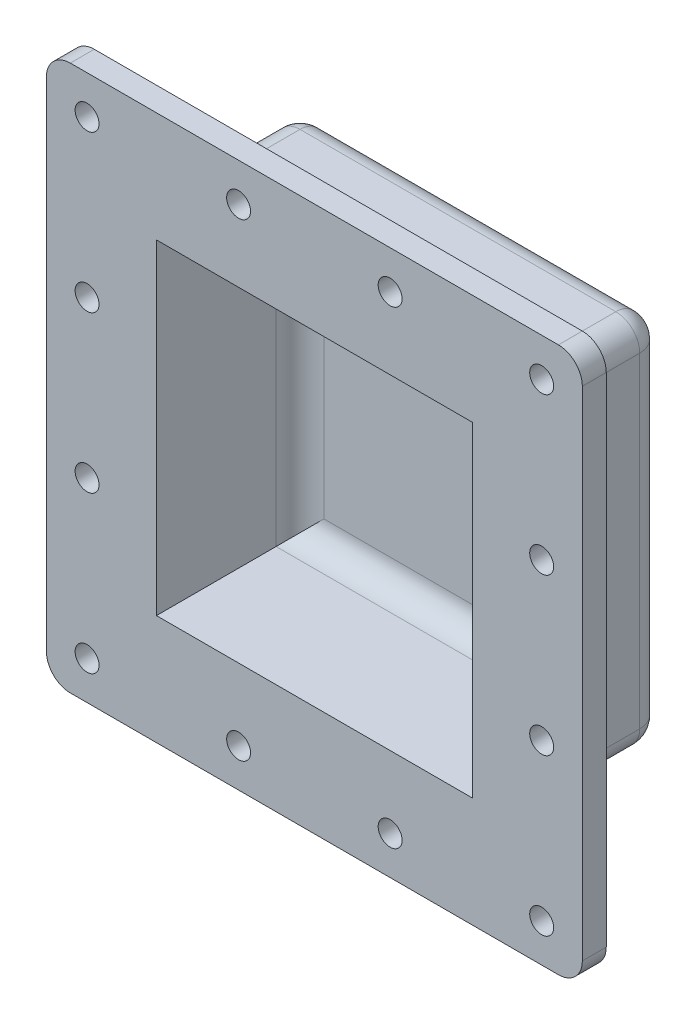
SolidWorks part; units mm, degrees
ref_plane "Front Plane" through (0, 0, 0) normal (0, 0, 1) x (1, 0, 0)
ref_plane "Top Plane" through (0, 0, 0) normal (0, 1, 0) x (1, 0, 0)
ref_plane "Right Plane" through (0, 0, 0) normal (1, 0, 0) x (0, 0, -1)
sketch "Sketch1" plane through (0, 0, 0) normal (0, 0, 1) x (1, 0, 0)
  line L1 (-19, 19.5) -> (19, 19.5)
  line L2 (-19, 19.5) -> (-19, -19.5)
  line L3 (-19, -19.5) -> (19, -19.5)
  line L4 (19, 19.5) -> (19, -19.5)
  line L5 (-19, 19.5) -> (19, -19.5) construction
  line L6 (-19, -19.5) -> (19, 19.5) construction
  point P0 (0, 0)
  dimension "D1" = 38
  dimension "D2" = 39
extrude "Boss-Extrude1" add sketch "Sketch1" along normal blind 15
sketch "Sketch2" plane through (0, 0, 15) normal (0, 0, 1) x (1, 0, 0)
  line L0 (-19, 19.5) -> (-19, -19.5) construction
  line L1 (-28, 28.5) -> (28, 28.5)
  line L2 (-28, 28.5) -> (-28, -28.5)
  line L3 (-28, -28.5) -> (28, -28.5)
  line L4 (28, 28.5) -> (28, -28.5)
  line L5 (-28, 28.5) -> (28, -28.5) construction
  line L6 (-28, -28.5) -> (28, 28.5) construction
  line L7 (-19, 19.5) -> (19, 19.5) construction
  point P0 (0, 0)
  dimension "D1" = 9
  dimension "D2" = 9
extrude "Boss-Extrude2" add sketch "Sketch2" along normal blind 2.5
shell "Shell1" thickness 2.5 removed face at (0, 0, 17.5)
fillet "Fillet1" radius 2.5 4 edges at (-28, -28.5, 16.25) (28, -28.5, 16.25) (28, 28.5, 16.25) (-28, 28.5, 16.25)
fillet "Fillet2" radius 2.5 12 edges at (0, -17, 2.5) (16.5, 0, 2.5) (-16.5, 0, 2.5) (0, 17, 2.5) (0, -19.5, 0) (19, 0, 0) (0, 19.5, 0) (-19, 0, 0) (19, -19.5, 7.5) (19, 19.5, 7.5) (-19, -19.5, 7.5) (-19, 19.5, 7.5)
sketch "Sketch3" plane through (0, 0, 2.5) normal (0, 0, 1) x (1, 0, 0)
  line L1 (-7.5, 14) -> (7.5, 14)
  line L2 (-7.5, 14) -> (-7.5, 6)
  line L3 (-7.5, 6) -> (7.5, 6)
  line L4 (7.5, 14) -> (7.5, 6)
  line L5 (-7.5, 14) -> (7.5, 6) construction
  line L6 (-7.5, 6) -> (7.5, 14) construction
  point P0 (0, 10)
  dimension "D1" = 8
  dimension "D2" = 15
  dimension "D3" = 10
extrude "Cut-Extrude1" cut sketch "Sketch3" against normal through all
sketch "Sketch4" plane through (0, 0, 17.5) normal (0, 0, 1) x (1, 0, 0)
  line L1 (-19, 19.5) -> (-19, -19.5) construction
  line L2 (-19, 19.5) -> (19, 19.5) construction
  line L3 (-23.75, 24.5) -> (23.75, 24.5) construction
  line L10 (-23.75, 24.5) -> (-23.75, -24.5) construction
  line L11 (-23.75, -24.5) -> (23.75, -24.5) construction
  line L18 (23.75, 24.5) -> (23.75, -24.5) construction
  line L19 (-23.75, 24.5) -> (23.75, -24.5) construction
  line L20 (-23.75, -24.5) -> (23.75, 24.5) construction
  circle A21 centre (-23.75, 24.5) radius 1.25
  circle A25 centre (-7.9167, 24.5) radius 1.25
  circle A26 centre (7.9167, 24.5) radius 1.25
  circle A27 centre (23.75, 24.5) radius 1.25
  circle A30 centre (23.75, 8.1667) radius 1.25
  circle A33 centre (23.75, -8.1667) radius 1.25
  circle A34 centre (-7.9167, -24.5) radius 1.25
  circle A35 centre (7.9167, -24.5) radius 1.25
  circle A36 centre (23.75, -24.5) radius 1.25
  circle A37 centre (-23.75, 8.1667) radius 1.25
  circle A38 centre (-23.75, -8.1667) radius 1.25
  circle A39 centre (-23.75, -24.5) radius 1.25
  circle A40 centre (-7.9167, 8.1667) radius 1.25 [skipped]
  circle A41 centre (7.9167, 8.1667) radius 1.25 [skipped]
  circle A42 centre (-7.9167, -8.1667) radius 1.25 [skipped]
  circle A43 centre (7.9167, -8.1667) radius 1.25 [skipped]
  point P0 (0, 0)
  dimension "D1" = 4.75
  dimension "D3" = 2.5
  dimension "D2" = 5
  dimension "D5" = 4
  dimension "D4" = 4
extrude "Cut-Extrude2" cut sketch "Sketch4" against normal up to surface (2.5 mm away) up to face at (0, 0, 15)
equation "\"case_width\"=38.00"
equation "\"D1@Sketch1\"=\"case_width\""
